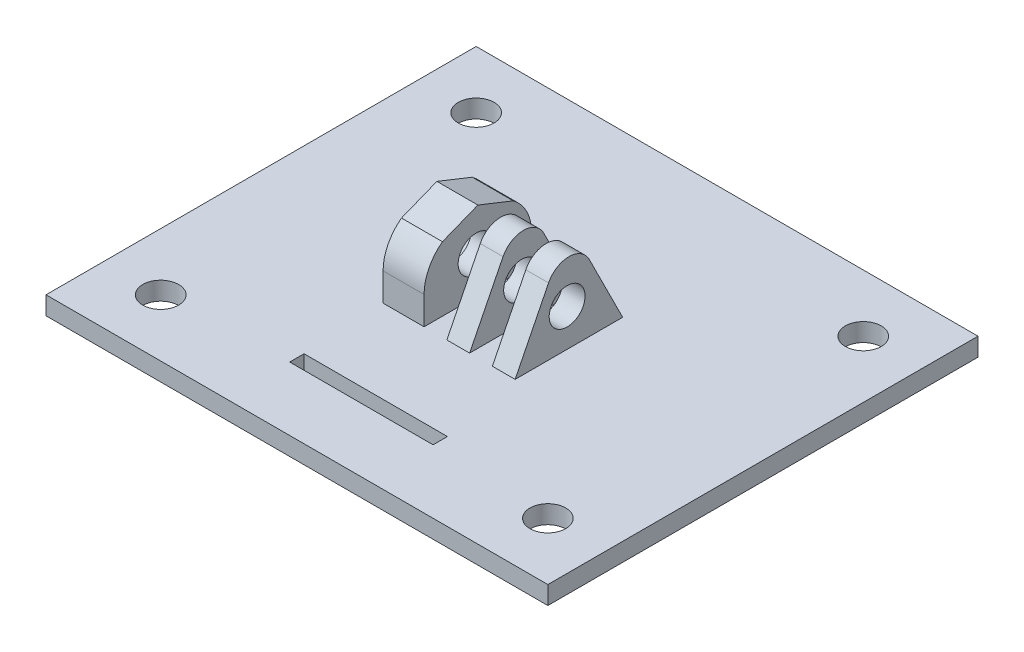
SolidWorks part; units mm, degrees
ref_plane "Front Plane" through (0, 0, 0) normal (0, 0, 1) x (1, 0, 0)
ref_plane "Top Plane" through (0, 0, 0) normal (0, 1, 0) x (1, 0, 0)
ref_plane "Right Plane" through (0, 0, 0) normal (1, 0, 0) x (0, 0, -1)
sketch "Sketch1" plane through (0, 0, 0) normal (0, 1, 0) x (1, 0, 0)
  line L0 (-35, 0) -> (-35, 60)
  line L1 (-35, 60) -> (35, 60)
  line L2 (-27, 52) -> (27, 52) construction
  line L3 (-27, 8) -> (27, 8) construction
  line L4 (-1.0399, 90.0475) -> (-1.0399, -44.0729) construction
  line L5 (83.9601, 90.0475) -> (-86.0399, 90.0475) construction
  line L6 (35, 60) -> (35, 0)
  line L7 (35, 0) -> (-35, 0)
  line L8 (-27, 60) -> (-27, 0) construction
  line L9 (27, 60) -> (27, 0) construction
  circle A0 centre (-27, 52) radius 2.5
  circle A1 centre (-27, 8) radius 2.5
  circle A2 centre (27, 52) radius 2.5
  circle A3 centre (27, 8) radius 2.5
  dimension "D2" = 8
  dimension "D4" = 5
  dimension "D1" = 8
  dimension "D3" = 70
  dimension "D5" = 60
  dimension "D6" = 8
  dimension "D7" = 8
extrude "Boss-Extrude1" add sketch "Sketch1" along normal blind 2.54
sketch "Sketch2" plane through (0, 0, 0) normal (1, 0, 0) x (0, 0, -1)
  line L0 (37.5, 2.54) -> (30, 17.54)
  line L1 (0, 2.54) -> (60, 2.54) construction
  line L2 (30, 17.54) -> (22.5, 2.54)
  line L3 (37.5, 2.54) -> (22.5, 2.54)
  line L4 (30, 2.54) -> (30, 0) construction
  line L5 (0, 2.54) -> (60, 2.54) construction
  line L6 (0, 0) -> (60, 0) construction
  circle A0 centre (30, 7.62) radius 1.651
  dimension "D2" = 3.302
  dimension "D1" = 15
  dimension "D3" = 15
  dimension "D4" = 5.08
extrude "Boss-Extrude2" add sketch "Sketch2" along normal mid plane 15.875 contours L3 L0 L2 | A0
sketch "Sketch3" plane through (0, 2.54, 0) normal (0, 1, 0) x (1, 0, 0)
  line L1 (7.9375, 37.5) -> (-7.9375, 37.5) construction
  line L2 (-4.7625, 37.5) -> (-1.5875, 37.5)
  line L3 (-4.7625, 37.5) -> (-4.7625, 22.5)
  line L4 (-4.7625, 22.5) -> (-1.5875, 22.5)
  line L6 (-1.5875, 37.5) -> (-1.5875, 22.5)
  line L8 (7.9375, 22.5) -> (-7.9375, 22.5) construction
  line L9 (1.5875, 37.5) -> (4.7625, 37.5)
  line L10 (1.5875, 37.5) -> (1.5875, 22.5)
  line L11 (1.5875, 22.5) -> (4.7625, 22.5)
  line L12 (4.7625, 37.5) -> (4.7625, 22.5)
  line L13 (-1.5875, 22.5) -> (1.5875, 22.5) construction
  line L14 (0, 22.5) -> (0, 0) construction
  line L15 (-35, 0) -> (35, 0) construction
  dimension "D1" = 3.175
  dimension "D2" = 3.175
extrude "Cut-Extrude1" cut sketch "Sketch3" along normal up to vertex
fillet "Fillet1" radius 3.175 3 edges at (6.35, 17.54, -30) (0, 17.54, -30) (-6.35, 17.54, -30)
sketch "Sketch6" plane through (-7.9375, 0, 0) normal (-1, 0, 0) x (0, 0, 1)
  line L1 (-22.5, 2.54) -> (-37.5, 2.54)
  line L2 (-22.5, 2.54) -> (-22.5, 12.7)
  line L3 (-22.5, 12.7) -> (-37.5, 12.7)
  line L4 (-37.5, 2.54) -> (-37.5, 12.7)
  circle A0 centre (-30, 7.62) radius 1.651
  circle A1 centre (-30, 7.62) radius 1.651 construction
  dimension "D1" = 10.16
extrude "Boss-Extrude5" add sketch "Sketch6" against normal up to surface (3.175 mm away) up to face at (-4.7625, 7.62, -31.651)
sketch "Sketch4" plane through (-7.9375, 0, 0) normal (-1, 0, 0) x (0, 0, 1)
  line L0 (-37.5, 12.7) -> (-37.5, 2.54) construction
  line L1 (-37.5, 2.54) -> (-22.5, 2.54)
  line L2 (-37.5, 2.54) -> (-37.5, 11.54)
  line L3 (-37.5, 11.54) -> (-22.5, 11.54)
  line L4 (-22.5, 2.54) -> (-22.5, 11.54)
  line L5 (-30, 2.8857) -> (-25.9, 5.2529)
  line L6 (-25.9, 5.2529) -> (-25.9, 9.9871)
  line L7 (-25.9, 9.9871) -> (-30, 12.3543)
  line L8 (-30, 12.3543) -> (-34.1, 9.9871)
  line L9 (-34.1, 9.9871) -> (-34.1, 5.2529)
  line L10 (-34.1, 5.2529) -> (-30, 2.8857)
  line L11 (-37.5, 2.54) -> (-22.5, 2.54) construction
  circle A0 centre (-30, 7.62) radius 4.1 construction
  circle A1 centre (-30, 7.62) radius 1.651 construction
  circle A2 centre (-30, 7.62) radius 1.651
  line M7 (-37.5, 2.54) -> (-22.5, 2.54)
  line M24 (-22.5, 2.54) -> (-22.5, 12.7)
  line M25 (-22.5, 12.7) -> (-27.7695, 12.7)
  line M26 (-37.5, 12.7) -> (-37.5, 2.54)
  dimension "D1" = 9
  dimension "D2" = 8.2
extrude "Boss-Extrude6" add sketch "Sketch4" along normal blind 2.54 contours L10 L9 L8 L7 L6 L5 M26 M7 M24 M25
fillet "Fillet2" radius 6.35 2 edges at (-6.35, 12.7, -22.5) (-6.35, 12.7, -37.5)
hole_wizard "Ø5.0mm Dowel Hole1" positions "Sketch8" profile "Sketch9" hole size "Ø5.0" standard "ISO"
sketch "Sketch8" plane through (7.9375, 0, 0) normal (1, 0, 0) x (0, 0, -1)
  point P0 (29.7511, 7.7409)
sketch "Sketch9" plane through (7.9375, 7.7409, -29.7511) normal (0, 1, 0) x (0, 0, -1)
  line L0 (0, 0) -> (0, 21.5022)
  line L1 (0, 21.5022) -> (2.5, 20)
  line L2 (2.5, 20) -> (2.5, 0)
  line L5 (2.5, 0) -> (0, 0)
  line L10 (0, 21.5022) -> (-2.5, 20) construction
  line L11 (0, -6.35) -> (0, 107.95) construction
  dimension "Hole Dia." = 5
  dimension "Hole Depth" = 20
  dimension "Drill Angle" = 118
sketch "Sketch10" plane through (0, 2.54, 0) normal (0, 1, 0) x (1, 0, 0)
  line L0 (0, 60) -> (-1.0399, 493.5128) construction
  line L1 (-9.8822, 10.8745) -> (10.1178, 10.8745)
  line L2 (-9.8822, 10.8745) -> (-9.8822, 8.8745)
  line L3 (-9.8822, 8.8745) -> (10.1178, 8.8745)
  line L4 (10.1178, 10.8745) -> (10.1178, 8.8745)
  line L5 (35, 60) -> (-35, 60) construction
  line L6 (-1.0399, 90.0475) -> (-1.0399, -29.9525) construction
  line L7 (17.5, 17.8745) -> (-17.5, 17.8745) construction
  dimension "D1" = 20
  dimension "D2" = 2
  dimension "D3" = 10
  dimension "D4" = 7
extrude "Cut-Extrude2" cut sketch "Sketch10" against normal blind 10
sketch "Sketch12" plane through (-7.9375, 0, 0) normal (-1, 0, 0) x (0, 0, 1)
  line L0 (-31.4104, 11.54) -> (-30, 12.3543)
  line L1 (-30, 12.3543) -> (-28.5896, 11.54)
  line L2 (-28.5896, 11.54) -> (-25.0633, 11.54)
  line L3 (-25.0633, 11.54) -> (-30, 13.5006)
  line L4 (-31.4104, 11.54) -> (-34.9367, 11.54)
  line L5 (-34.9367, 11.54) -> (-30, 13.5006)
  arc A1 (-32.2305, 12.7) -> (-34.9367, 11.54) centre (-31.15, 6.4426) ccw construction
extrude "Boss-Extrude8" add sketch "Sketch12" against normal up to surface (2.54 mm away)
sketch "Sketch13" plane through (-7.9375, 0, 0) normal (-1, 0, 0) x (0, 0, 1)
  line L2 (-34.9367, 11.54) -> (-30, 13.5006)
  line L3 (-30, 13.5006) -> (-25.0633, 11.54)
  line L4 (-34.9367, 11.54) -> (-30, 13.5006)
  line L5 (-30, 13.5006) -> (-25.0633, 11.54)
  arc A3 (-25.0633, 11.54) -> (-27.7695, 12.7) centre (-28.85, 6.4426) ccw
  arc A4 (-27.7695, 12.7) -> (-32.2305, 12.7) centre (-30, 10.4405) ccw
  arc A5 (-32.2305, 12.7) -> (-34.9367, 11.54) centre (-31.15, 6.4426) ccw
  arc A6 (-25.0633, 11.54) -> (-27.7695, 12.7) centre (-28.85, 6.4426) ccw
  arc A7 (-27.7695, 12.7) -> (-32.2305, 12.7) centre (-30, 10.4405) ccw
  arc A8 (-32.2305, 12.7) -> (-34.9367, 11.54) centre (-31.15, 6.4426) ccw
  dimension "D1" = 0
extrude "Cut-Extrude3" cut sketch "Sketch13" against normal up to surface (6.35 mm away) up to face at (-1.5875, 7.7409, -27.2511)
